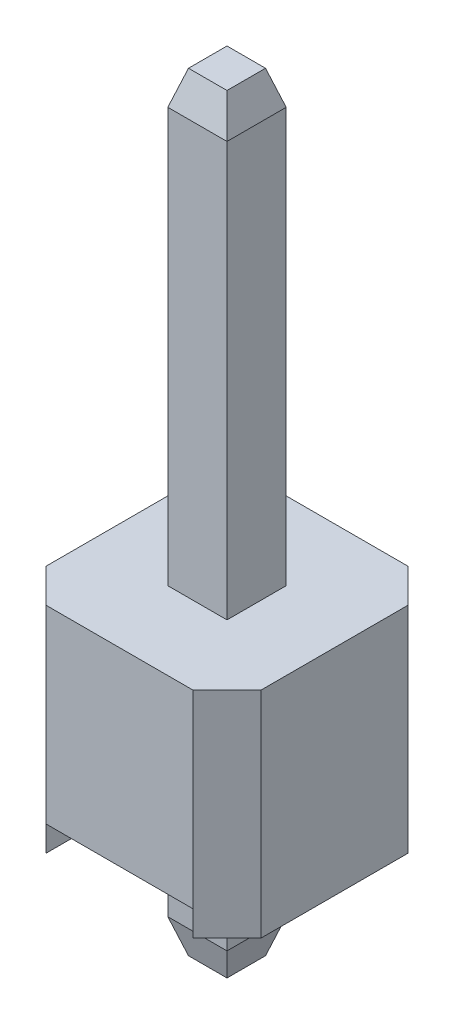
SolidWorks part; units mm, degrees
ref_plane "Front Plane" through (0, 0, 0) normal (0, 0, 1) x (1, 0, 0)
ref_plane "Top Plane" through (0, 0, 0) normal (0, 1, 0) x (1, 0, 0)
ref_plane "Right Plane" through (0, 0, 0) normal (1, 0, 0) x (0, 0, -1)
sketch "Sketch1" plane through (0, 0, 0) normal (0, 1, 0) x (1, 0, 0)
  line L1 (-1.27, 1.27) -> (1.27, 1.27)
  line L2 (-1.27, 1.27) -> (-1.27, -1.27)
  line L3 (-1.27, -1.27) -> (1.27, -1.27)
  line L4 (1.27, 1.27) -> (1.27, -1.27)
  line L5 (-1.27, 1.27) -> (1.27, -1.27) construction
  line L6 (-1.27, -1.27) -> (1.27, 1.27) construction
  point P0 (0, 0)
  dimension "D1" = 2.54
  dimension "D2" = 2.54
extrude "Boss-Extrude1" add sketch "Sketch1" along normal blind 2.54
chamfer "Chamfer1" distance 0.4 angle 45 4 edges at (-1.27, 1.27, -1.27) (1.27, 1.27, -1.27) (-1.27, 1.27, 1.27) (1.27, 1.27, 1.27)
sketch "Sketch2" plane through (0, 0, 0) normal (0, -1, 0) x (1, 0, 0)
  line L1 (-0.87, 1.27) -> (0.87, 1.27)
  line L2 (-0.87, 1.27) -> (-0.87, -1.27)
  line L3 (-0.87, -1.27) -> (0.87, -1.27)
  line L4 (0.87, 1.27) -> (0.87, -1.27)
extrude "Cut-Extrude1" cut sketch "Sketch2" against normal blind 0.3
sketch "Sketch3" plane through (0, 2.54, 0) normal (0, 1, 0) x (1, 0, 0)
  line L1 (0.35, 0.35) -> (-0.35, 0.35)
  line L2 (0.35, 0.35) -> (0.35, -0.35)
  line L3 (0.35, -0.35) -> (-0.35, -0.35)
  line L4 (-0.35, 0.35) -> (-0.35, -0.35)
  line L5 (0.35, 0.35) -> (-0.35, -0.35) construction
  line L6 (0.35, -0.35) -> (-0.35, 0.35) construction
  point P0 (0, 0)
  dimension "D1" = 0.7
  dimension "D2" = 0.7
extrude "Boss-Extrude2" add sketch "Sketch3" along normal blind 5.3
sketch "Sketch4" plane through (0, 0.3, 0) normal (0, -1, 0) x (1, 0, 0)
  line L0 (-0.35, 0.35) -> (0.35, 0.35) construction
  line L1 (-0.35, 0.35) -> (0.35, 0.35)
  line L2 (-0.35, 0.35) -> (-0.35, -0.35)
  line L3 (-0.35, -0.35) -> (0.35, -0.35)
  line L4 (0.35, 0.35) -> (0.35, -0.35)
  line L5 (-0.35, 0.35) -> (0.35, -0.35) construction
  line L6 (-0.35, -0.35) -> (0.35, 0.35) construction
  line L7 (0.35, 0.35) -> (0.35, -0.35) construction
  point P0 (0, 0)
extrude "Boss-Extrude3" add sketch "Sketch4" along normal blind 1.55
chamfer "Chamfer2" distance 0.4 angle 17 8 edges at (0, 7.84, -0.35) (-0.35, 7.84, 0) (0.35, 7.84, 0) (0, 7.84, 0.35) (0, -1.25, -0.35) (-0.35, -1.25, 0) (0.35, -1.25, 0) (0, -1.25, 0.35) first distance on face at (0, 5.19, -0.35) first distance on face at (-0.35, 5.19, 0) first distance on face at (0.35, 5.19, 0) first distance on face at (0, 5.19, 0.35) first distance on face at (0, -0.475, -0.35) first distance on face at (-0.35, -0.475, 0) first distance on face at (0.35, -0.475, 0) first distance on face at (0, -0.475, 0.35)
ref_axis "Center" through (0, 8.2945, 0) along (0, -1, 0)
